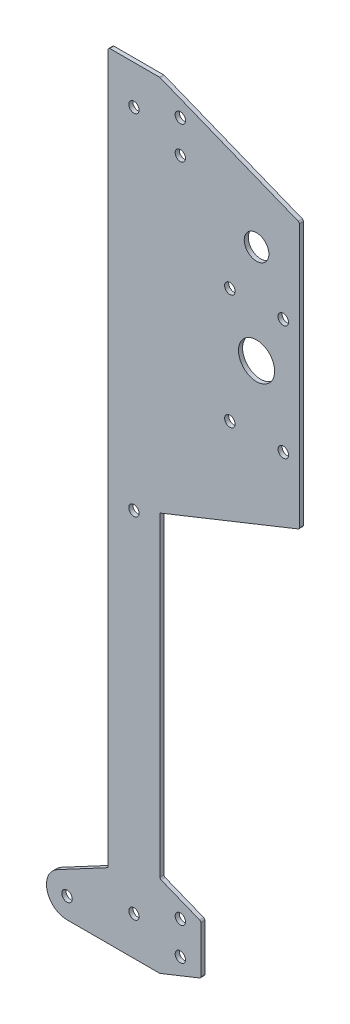
SolidWorks part; units mm, degrees
ref_plane "Front Plane" through (0, 0, 0) normal (0, 0, 1) x (1, 0, 0)
ref_plane "Top Plane" through (0, 0, 0) normal (0, 1, 0) x (1, 0, 0)
ref_plane "Right Plane" through (0, 0, 0) normal (1, 0, 0) x (0, 0, -1)
sketch "Sketch1" plane through (0, 0, 0) normal (0, 0, 1) x (1, 0, 0)
  line L1 (-10, 150) -> (10, 150)
  line L2 (-10, 150) -> (-10, -150)
  line L3 (-10, -150) -> (10, -150)
  line L4 (10, 150) -> (10, -150)
  line L5 (-10, 150) -> (10, -150) construction
  line L6 (-10, -150) -> (10, 150) construction
  point P0 (0, 0)
  dimension "D1" = 300
  dimension "20mm" = 20
extrude "Boss-Extrude1" add sketch "Sketch1" along normal blind 1.5875
sketch "Sketch2" plane through (0, 0, 1.5875) normal (0, 0, 1) x (1, 0, 0)
  line L0 (10, 150) -> (25.875, 143.65)
  line L1 (25.875, 143.65) -> (25.875, 124.6)
  line L2 (25.875, 124.6) -> (10, 118.25)
  line L3 (10, -150) -> (10, 150) construction
  line L4 (10, 118.25) -> (10, 150)
  line L5 (10, 150) -> (-10, 150) construction
  line L6 (-10, 0) -> (10, 0) construction
  line L7 (-10, 150) -> (-10, -150) construction
  line L8 (10, -118.25) -> (10, -150)
  line L9 (25.875, -124.6) -> (10, -118.25)
  line L10 (25.875, -143.65) -> (25.875, -124.6)
  line L11 (10, -150) -> (25.875, -143.65)
  circle A0 centre (17.9375, 127.775) radius 2
  circle A1 centre (17.9375, 127.775) radius 5 construction
  circle A2 centre (17.9375, 140.475) radius 2
  circle A3 centre (17.9375, -140.475) radius 2
  circle A4 centre (17.9375, -127.775) radius 5 construction
  circle A5 centre (17.9375, -127.775) radius 2
  point P3 (25.875, 134.125)
  point P8 (10, 134.125)
  point P13 (17.9375, 121.425)
  dimension "D3" = 4
  dimension "D4" = 10
  dimension "D1" = 15.875
  dimension "2.5" = 31.75
  dimension "D2" = 19.05
  dimension "D5" = 9.525
  dimension "D6" = 9.525
extrude "Boss-Extrude2" add sketch "Sketch2" against normal up to surface (1.5875 mm away) up to face at (0, 0, 0)
sketch "Sketch4" plane through (0, 0, 1.5875) normal (0, 0, 1) x (1, 0, 0)
  line L0 (0, 150) -> (0, 135) construction
  line L1 (10, 150) -> (-10, 150) construction
  line L2 (0, 135) -> (0, 0) construction
  line L3 (0, 0) -> (0, -135) construction
  line L4 (0, -135) -> (0, -150) construction
  line L5 (-10, -150) -> (10, -150) construction
  circle A0 centre (0, -135) radius 2
  circle A1 centre (0, 0) radius 2
  circle A2 centre (0, 135) radius 2
  dimension "D4" = 4
  dimension "D1" = 15
  dimension "D2" = 135
  dimension "D3" = 135
extrude "Cut-Extrude1" cut sketch "Sketch4" against normal through all
sketch "Sketch5" plane through (0, 0, 1.5875) normal (0, 0, 1) x (1, 0, 0)
  line L0 (-10, 111.9) -> (-41.75, 118.25)
  line L1 (-10, 150) -> (-10, -150) construction
  line L2 (-41.75, 118.25) -> (-41.75, 137.3)
  line L3 (-41.75, 137.3) -> (-10, 137.3)
  line L4 (-10, 137.3) -> (-10, 111.9)
  line L5 (10, 150) -> (-10, 150) construction
  line L6 (-41.75, 133.3313) -> (-37.7813, 133.3313) construction
  line L7 (-13.9688, 133.3313) -> (-10, 133.3313) construction
  line L8 (-10, -150) -> (-25.875, -150)
  line L9 (-29.6103, -135.0588) -> (-10, -124.6)
  line L10 (-10, -124.6) -> (-10, -150)
  circle A0 centre (-13.9688, 133.3313) radius 2.032
  circle A1 centre (-13.9688, 122.2188) radius 2.032
  circle A2 centre (-37.7813, 133.3313) radius 2.032
  circle A3 centre (-37.7813, 122.2188) radius 2.032
  arc A4 (-25.875, -150) -> (-29.6103, -135.0588) centre (-25.875, -142.0625) cw
  circle A5 centre (-25.875, -142.0625) radius 2.032
  point P24 (-25.875, 137.3)
  dimension "D5" = 4.064
  dimension "D9" = 4.064
  dimension "D10" = 7.9375
  dimension "D1" = 12.7
  dimension "D2" = 19.05
  dimension "D3" = 25.4
  dimension "D4" = 31.75
  dimension "D6" = 11.1125
  dimension "D7" = 23.8125
  dimension "D8" = 3.9688
  dimension "D11" = 25.4
extrude "Boss-Extrude3" [suppressed] add sketch "Sketch5" against normal up to surface (1.5875 mm away) up to face at (2, -135, 0)
fillet "Fillet3" [suppressed] radius 1.5875
sketch "Sketch6" plane through (0, 0, 1.5875) normal (0, 0, 1) x (1, 0, 0)
  line L0 (-10, -124.6) -> (-10, -150) construction
  line L1 (-10, -150) -> (-25.875, -150) construction
  line L2 (-29.6103, -135.0588) -> (-10, -124.6) construction
  line L3 (-10, -124.6) -> (-10, -150)
  line L4 (-10, -150) -> (-25.875, -150)
  line L5 (-29.6103, -135.0588) -> (-10, -124.6)
  circle A0 centre (-25.875, -142.0625) radius 2.032 construction
  arc A1 (-29.6103, -135.0588) -> (-25.875, -150) centre (-25.875, -142.0625) ccw construction
  circle A2 centre (-25.875, -142.0625) radius 2.032
  arc A3 (-29.6103, -135.0588) -> (-25.875, -150) centre (-25.875, -142.0625) ccw
extrude "Boss-Extrude4" add sketch "Sketch6" against normal up to vertex (1.5875 mm away) up to point (-10, -150, 0)
fillet "Fillet4" radius 0.7937 10 edges at (10, 118.25, 0.7937) (25.875, 124.6, 0.7937) (-10, 150, 0.7937) (10, 150, 0.7937) (25.875, 143.65, 0.7937) (-10, -124.6, 0.7937) (10, -118.25, 0.7937) (25.875, -124.6, 0.7937) (25.875, -143.65, 0.7937) (10, -150, 0.7937)
fillet "Fillet5" [suppressed] radius 1.5875
sketch "Sketch7" plane through (0, 0, 0) normal (0, 0, -1) x (-1, 0, 0)
  line L0 (-25.376, 143.8496) -> (-63.476, 128.6096)
  line L1 (-63.975, 127.8726) -> (-63.975, 26.2726)
  line L2 (-63.476, 25.5356) -> (-10, 4.1452)
  line L3 (-10, -117.7126) -> (-10, 117.7126) construction
  line L4 (-10, 4.1452) -> (-10, 117.7126)
  line L5 (-25.875, 143.1126) -> (-25.875, 125.1374) construction
  line L6 (-25.376, 124.4004) -> (-10.499, 118.4496) construction
  line L7 (-25.875, 143.1126) -> (-25.875, 125.1374)
  line L8 (-25.376, 124.4004) -> (-10.499, 118.4496)
  line L9 (-10.1419, 149.9432) -> (-25.376, 143.8496) construction
  line L10 (-9.8471, 150) -> (9.2063, 150) construction
  line L11 (-47.4015, 70.625) -> (-47.4015, 73.8) construction
  line L12 (-37.0828, 48.4) -> (-57.7203, 48.4) construction
  line L13 (-37.0828, 48.4) -> (-37.0828, 92.85) construction
  line L14 (-37.0828, 92.85) -> (-57.7203, 92.85) construction
  line L15 (-57.7203, 48.4) -> (-57.7203, 92.85) construction
  line L16 (-37.0828, 48.4) -> (-57.7203, 92.85) construction
  line L17 (-37.0828, 92.85) -> (-57.7203, 48.4) construction
  line L18 (-47.4015, 111.9) -> (-47.4015, 73.8) construction
  arc A0 (-63.476, 128.6096) -> (-63.975, 127.8726) centre (-63.1812, 127.8726) ccw
  arc A1 (-63.975, 26.2726) -> (-63.476, 25.5356) centre (-63.1812, 26.2726) ccw
  arc A2 (-25.376, 143.8496) -> (-25.875, 143.1126) centre (-25.0813, 143.1126) ccw construction
  arc A3 (-25.875, 125.1374) -> (-25.376, 124.4004) centre (-25.0813, 125.1374) ccw construction
  arc A4 (-10, 117.7126) -> (-10.499, 118.4496) centre (-10.7937, 117.7126) ccw construction
  arc A5 (-25.376, 143.8496) -> (-25.875, 143.1126) centre (-25.0813, 143.1126) ccw
  arc A6 (-25.875, 125.1374) -> (-25.376, 124.4004) centre (-25.0813, 125.1374) ccw
  arc A7 (-10, 117.7126) -> (-10.499, 118.4496) centre (-10.7937, 117.7126) ccw
  arc A8 (10, 149.2063) -> (9.2063, 150) centre (9.2063, 149.2063) ccw construction
  circle A9 centre (-47.4015, 111.9) radius 4.7625
  circle A10 centre (-47.4015, 73.8) radius 6.985
  circle A11 centre (-57.7203, 92.85) radius 2.032
  circle A12 centre (-57.7203, 48.4) radius 2.032
  circle A13 centre (-37.0828, 48.4) radius 2.032
  circle A14 centre (-37.0828, 92.85) radius 2.032
  point P32 (-47.4015, 70.625)
  dimension "D4" = 9.525
  dimension "D6" = 13.97
  dimension "D11" = 4.064
  dimension "D1" = 38.1
  dimension "D2" = 101.6
  dimension "D3" = 16.5735
  dimension "D5" = 38.1
  dimension "D7" = 3.175
  dimension "D8" = 44.45
  dimension "D9" = 38.1
  dimension "D10" = 20.6375
extrude "Boss-Extrude5" add sketch "Sketch7" against normal up to surface (1.5875 mm away) up to face at (2, -135, 1.5875)
